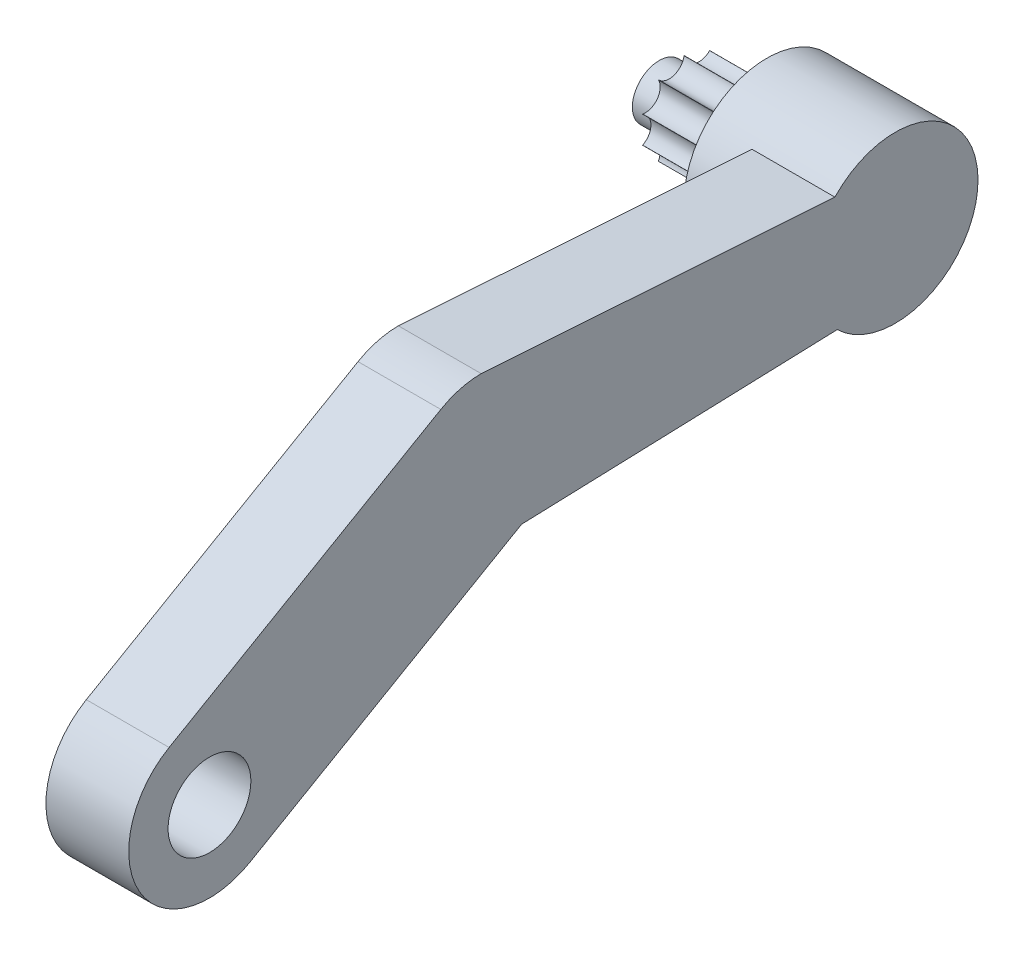
SolidWorks part; units mm, degrees
ref_plane "正面" through (0, 0, 0) normal (0, 0, 1) x (1, 0, 0)
ref_plane "平面" through (0, 0, 0) normal (0, 1, 0) x (1, 0, 0)
ref_plane "右側面" through (0, 0, 0) normal (1, 0, 0) x (0, 0, -1)
sketch "ｽｹｯﾁ1" plane through (0, 0, 0) normal (1, 0, 0) x (0, 0, -1)
  line L0 (0, 0) -> (-100, 0) construction
  line L1 (-100, 0) -> (-165.6285, -37.8907) construction
  line L2 (-109.75, 16.8875) -> (-175.3785, -21.0032)
  line L3 (-90.25, -16.8875) -> (-155.8785, -54.7782)
  line L4 (-14.5648, 13.7064) -> (-100, 19.5)
  line L5 (-13.995, -14.2878) -> (-90.25, -16.8875)
  line L6 (-20, 0) -> (-20, 14.075) construction
  line L7 (-20, -14.4925) -> (-20, 0) construction
  circle A0 centre (0, 0) radius 20
  circle A1 centre (-165.6285, -37.8907) radius 10
  circle A2 centre (-165.6285, -37.8907) radius 19.5
  circle A3 centre (-100, 0) radius 19.5
  dimension "D1" = 40
  dimension "D5" = 20
  dimension "D6" = 39
  dimension "D7" = 39
  dimension "D2" = 65.6285
  dimension "D3" = 150
  dimension "D4" = 100
  dimension "D8" = 28
  dimension "D9" = 14.075
extrude "ﾎﾞｽ - 押し出し2" add sketch "ｽｹｯﾁ1" along normal blind 10 and the other way blind 10 contours L4 A3 | A3 L2 A2 L3 | A2 A1 | A3 L5 A0 L4 | A0 region at (0, -18.9453, 132.8143) region at (0, -0.0013, 100.0001) region at (0, -21.4808, 156.1543) region at (0, 0.465, 52.2265) region at (0, 0, 0)
sketch "ｽｹｯﾁ4" plane through (-10, 0, 0) normal (-1, 0, 0) x (0, 0, 1)
  circle A0 centre (0, 0) radius 20
  dimension "D1" = 40
extrude "ﾎﾞｽ - 押し出し4" add sketch "ｽｹｯﾁ4" along normal blind 11
sketch "ｽｹｯﾁ5" plane through (-21, 0, 0) normal (-1, 0, 0) x (0, 0, 1)
  circle A0 centre (0, 0) radius 10.5
extrude "ﾎﾞｽ - 押し出し5" add sketch "ｽｹｯﾁ5" along normal blind 26
sketch "ｽｹｯﾁ6" plane through (-47, 0, 0) normal (-1, 0, 0) x (0, 0, 1)
  circle A0 centre (0, 0) radius 6.5
  circle A1 centre (0, 0) radius 10.5
  circle M2 centre (0, 0) radius 10.5
  dimension "D1" = 13
  dimension "D2" = 21
extrude "ｶｯﾄ - 押し出し1" cut sketch "ｽｹｯﾁ6" against normal blind 6 contours A0 M2 region at (-47, 0, -10.203)
sketch "ｽｹｯﾁ7" plane through (-41, 0, 0) normal (-1, 0, 0) x (0, 0, 1)
  line L0 (0, 0) -> (0, 20) construction
  circle A0 centre (0, 0) radius 20 construction
  circle A1 centre (0, 0) radius 8 construction
  circle A2 centre (0, 0) radius 10.5 construction
  arc A3 (0, 10.5) -> (6.1382, 8.5189) centre (3.5648, 11.0452) ccw
  arc A4 (6.1717, 8.4947) -> (9.9732, 3.284) centre (9.3762, 6.8404) ccw
  arc A5 (9.9861, 3.2447) -> (9.9988, -3.2053) centre (11.6062, 0.0229) ccw
  arc A6 (9.9861, -3.2447) -> (6.2052, -8.4703) centre (9.4031, -6.8035) ccw
  arc A7 (6.1717, -8.4947) -> (0.0414, -10.4999) centre (3.6083, -11.0311) ccw
  arc A8 (0, -10.5) -> (-6.1382, -8.5189) centre (-3.5648, -11.0452) ccw
  arc A9 (-6.1717, -8.4947) -> (-9.9732, -3.284) centre (-9.3762, -6.8404) ccw
  arc A10 (-9.9861, -3.2447) -> (-9.9988, 3.2053) centre (-11.6062, -0.0229) ccw
  arc A11 (-9.9861, 3.2447) -> (-6.2052, 8.4703) centre (-9.4031, 6.8035) ccw
  arc A12 (-6.1717, 8.4947) -> (-0.0414, 10.4999) centre (-3.6083, 11.0311) ccw
  circle A13 centre (0, 0) radius 10.5
  point P39 (0.0666, -0.1591)
  point P40 (0, 0)
  circle M15 centre (0, 0) radius 10.5
  dimension "D1" = 40
  dimension "D2" = 16
  dimension "D3" = 21
  dimension "D5" = 10
  dimension "D6" = 0.0414
  dimension "D7" = 6.8035
  dimension "D4" = 6.45
extrude "ｶｯﾄ - 押し出し2" cut sketch "ｽｹｯﾁ7" against normal blind 18 contours A12 M15 | A3 M15 | A4 M15 | A5 M15 | A6 M15 | A7 M15 | A8 M15 | A9 M15 | A10 M15 | A11 M15 region at (-41, 8.9171, 2.8779) region at (-41, 8.9057, -2.9131) region at (-41, 5.5225, 7.5697) region at (-41, 5.4926, -7.5914) region at (-41, 0.0185, 9.37) region at (-41, -0.0185, -9.37) region at (-41, -5.4926, 7.5914) region at (-41, -5.5225, -7.5697) region at (-41, -8.9057, 2.9131) region at (-41, -8.9171, -2.8779)
